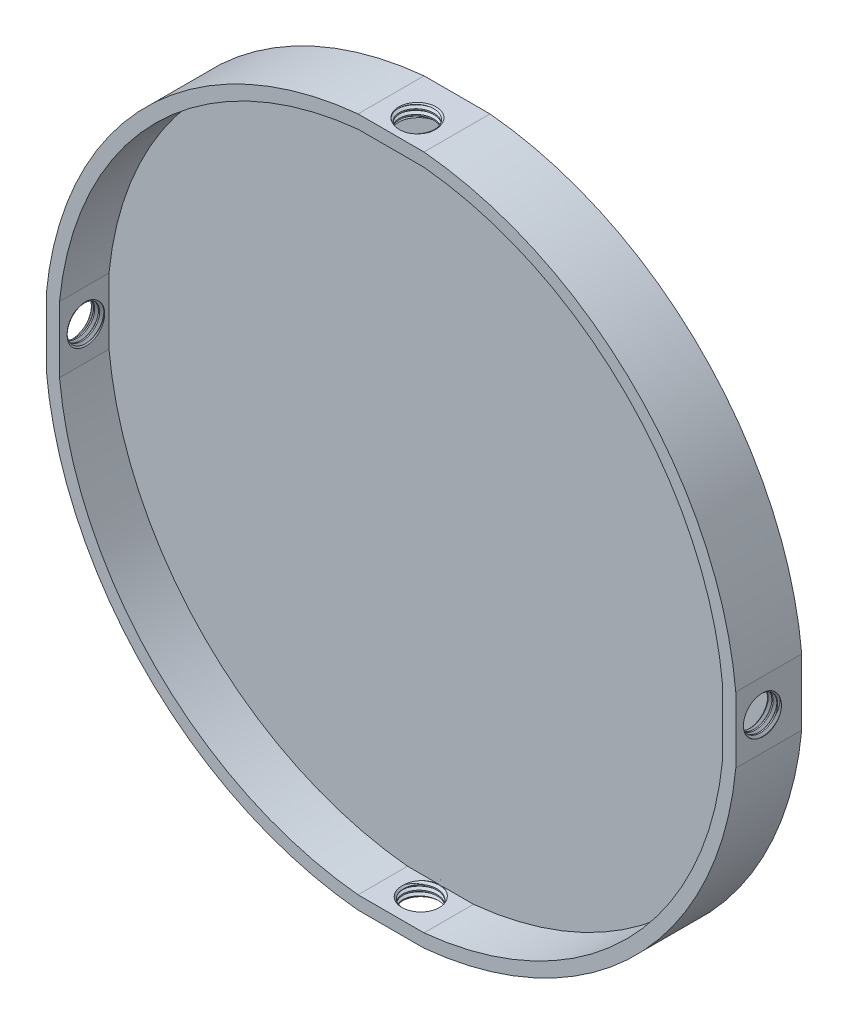
SolidWorks part; units mm, degrees
ref_plane "Front Plane" through (0, 0, 0) normal (0, 0, 1) x (1, 0, 0)
ref_plane "Top Plane" through (0, 0, 0) normal (0, 1, 0) x (1, 0, 0)
ref_plane "Right Plane" through (0, 0, 0) normal (1, 0, 0) x (0, 0, -1)
sketch "Sketch2" plane through (0, 0, 0) normal (0, 0, 1) x (1, 0, 0)
  circle A0 centre (0, 0) radius 105
  dimension "D1" = 210
extrude "Boss-Extrude1" add sketch "Sketch2" against normal blind 5 and the other way blind 15
sketch "Sketch4" plane through (0, 0, 15) normal (0, 0, 1) x (1, 0, 0)
  line L0 (-10, 104.5227) -> (10, 104.5227)
  line L1 (11, 0) -> (-11, 0) construction
  line L2 (-10, -104.5227) -> (10, -104.5227)
  line L3 (-104.5227, 10) -> (-104.5227, -10)
  line L4 (0, -11) -> (0, 11) construction
  line L5 (104.5227, 10) -> (104.5227, -10)
  arc A0 (-10, 104.5227) -> (-104.5227, 10) centre (0, 0) ccw
  arc A1 (10, -104.5227) -> (104.5227, -10) centre (0, 0) ccw
  arc A2 (-104.5227, -10) -> (-10, -104.5227) centre (0, 0) ccw
  arc A3 (104.5227, 10) -> (10, 104.5227) centre (0, 0) ccw
  dimension "D2" = 210
  dimension "D1" = 20
  dimension "D3" = 20
extrude "Cut-Extrude2" cut sketch "Sketch4" against normal through all flip side to cut
sketch "Sketch5" plane through (0, 0, 15) normal (0, 0, 1) x (1, 0, 0)
  line L0 (-10, 100.5037) -> (10, 100.5037)
  line L1 (11, 0) -> (-11, 0) construction
  line L2 (-10, -100.5037) -> (10, -100.5037)
  line L3 (-100.5037, 10) -> (-100.5037, -10)
  line L4 (0, -11) -> (0, 11) construction
  line L5 (100.5037, 10) -> (100.5037, -10)
  arc A0 (-100.5037, -10) -> (-10, -100.5037) centre (0, 0) ccw
  arc A1 (-10, 100.5037) -> (-100.5037, 10) centre (0, 0) ccw
  arc A2 (100.5037, 10) -> (10, 100.5037) centre (0, 0) ccw
  arc A3 (10, -100.5037) -> (100.5037, -10) centre (0, 0) ccw
  dimension "D1" = 202
  dimension "D2" = 20
  dimension "D3" = 20
extrude "Cut-Extrude3" cut sketch "Sketch5" against normal blind 15
sketch "Sketch6" plane through (0, -104.5227, 0) normal (0, -1, 0) x (-1, 0, 0)
  circle A0 centre (0, -6) radius 5.19
  dimension "D1" = 10.38
extrude "Cut-Extrude5" cut sketch "Sketch6" against normal blind 15
chamfer "Chamfer1" distance 0.5 angle 45 1 edges at (0, -104.5227, 0.81)
chamfer "Chamfer2" distance 0.5 angle 45 1 edges at (0, -100.5037, 0.81)
thread "Thread1" pitch 1.5 start angle 0, offset 2, length 0, pitch 1.5, diameter 10.38
ref_plane "Plane3" through (5.19, -106.0227, 6) normal (0, 0, 1) x (1, 0, 0)
sketch "Thread Profile3" plane through (5.19, -106.0227, 6) normal (0, 0, 1) x (1, 0, 0)
  line L0 (0, 0) -> (0, 1.5) construction
  line L1 (0, 0) -> (0.8119, 0.4687)
  line L2 (0.8119, 0.4687) -> (0.8119, 0.6562)
  line L3 (0.8119, 0.6562) -> (0, 1.125)
  line L4 (0.8119, 0.5625) -> (0, 0.5625) construction
  line L11 (0, 0) -> (0, 1.125)
  point P2 (0, 0)
  dimension "Pitch" = 1.5
  dimension "Profile_Angle" = 60
  dimension "Profile_Land" = 0.1875
  dimension "Profile_Height" = 0.8119
sketch "Sketch7" plane through (0, 104.5227, 0) normal (0, 1, 0) x (1, 0, 0)
  circle A0 centre (0, -7) radius 5.19
  dimension "D1" = 10.38
extrude "Cut-Extrude6" cut sketch "Sketch7" against normal blind 10
chamfer "Chamfer3" distance 0.5 angle 45 2 edges at (0, 100.5037, 12.19) (0, 104.5227, 12.19)
thread "Thread2" pitch 1.5 profile "Thread Profile4" start angle 0, offset 2, length 0, pitch 1.5, diameter 10.38
ref_plane "Plane4" through (-5.19, 106.0227, 7) normal (0, 0, 1) x (-1, 0, 0)
sketch "Thread Profile4" plane through (-5.19, 106.0227, 7) normal (0, 0, 1) x (-1, 0, 0)
  line L0 (0, 0) -> (0, 1.5) construction
  line L1 (0, 0) -> (0.8119, 0.4687)
  line L2 (0.8119, 0.4687) -> (0.8119, 0.6562)
  line L3 (0.8119, 0.6562) -> (0, 1.125)
  line L4 (0.8119, 0.5625) -> (0, 0.5625) construction
  line L11 (0, 0) -> (0, 1.125)
  point P2 (0, 0)
  dimension "Pitch" = 1.5
  dimension "Profile_Angle" = 60
  dimension "Profile_Land" = 0.1875
  dimension "Profile_Height" = 0.8119
sketch "Sketch10" plane through (-104.5227, 0, 0) normal (-1, 0, 0) x (0, 0, 1)
  circle A0 centre (7, 0) radius 5.19
  dimension "D1" = 10.38
extrude "Cut-Extrude7" cut sketch "Sketch10" against normal blind 10
chamfer "Chamfer4" distance 0.5 angle 45 2 edges at (-100.5037, 0, 12.19) (-104.5227, 0, 12.19)
thread "Thread3" pitch 1.5 profile "Thread Profile5" start angle 0, offset 2, length 0, pitch 1.5, diameter 10.38
ref_plane "Plane5" through (-106.0227, 0, 1.81) normal (0, -1, 0) x (0, 0, -1)
sketch "Thread Profile5" plane through (-106.0227, 0, 1.81) normal (0, -1, 0) x (0, 0, -1)
  line L0 (0, 0) -> (0, 1.5) construction
  line L1 (0, 0) -> (0.8119, 0.4687)
  line L2 (0.8119, 0.4687) -> (0.8119, 0.6562)
  line L3 (0.8119, 0.6562) -> (0, 1.125)
  line L4 (0.8119, 0.5625) -> (0, 0.5625) construction
  line L11 (0, 0) -> (0, 1.125)
  point P2 (0, 0)
  dimension "Pitch" = 1.5
  dimension "Profile_Angle" = 60
  dimension "Profile_Land" = 0.1875
  dimension "Profile_Height" = 0.8119
sketch "Sketch13" plane through (104.5227, 0, 0) normal (1, 0, 0) x (0, 0, -1)
  circle A0 centre (-7, 0) radius 5.19
  dimension "D1" = 10.38
extrude "Cut-Extrude8" cut sketch "Sketch13" against normal blind 10
chamfer "Chamfer5" distance 0.5 angle 45 2 edges at (100.5037, 0, 1.81) (104.5227, 0, 1.81)
thread "Thread4" pitch 1.5 profile "Thread Profile6" start angle 0, offset 2, length 0, pitch 1.5, diameter 10.38
ref_plane "Plane6" through (106.0227, 0, 12.19) normal (0, -1, 0) x (0, 0, 1)
sketch "Thread Profile6" plane through (106.0227, 0, 12.19) normal (0, -1, 0) x (0, 0, 1)
  line L0 (0, 0) -> (0, 1.5) construction
  line L1 (0, 0) -> (0.8119, 0.4687)
  line L2 (0.8119, 0.4687) -> (0.8119, 0.6562)
  line L3 (0.8119, 0.6562) -> (0, 1.125)
  line L4 (0.8119, 0.5625) -> (0, 0.5625) construction
  line L11 (0, 0) -> (0, 1.125)
  point P2 (0, 0)
  dimension "Pitch" = 1.5
  dimension "Profile_Angle" = 60
  dimension "Profile_Land" = 0.1875
  dimension "Profile_Height" = 0.8119
